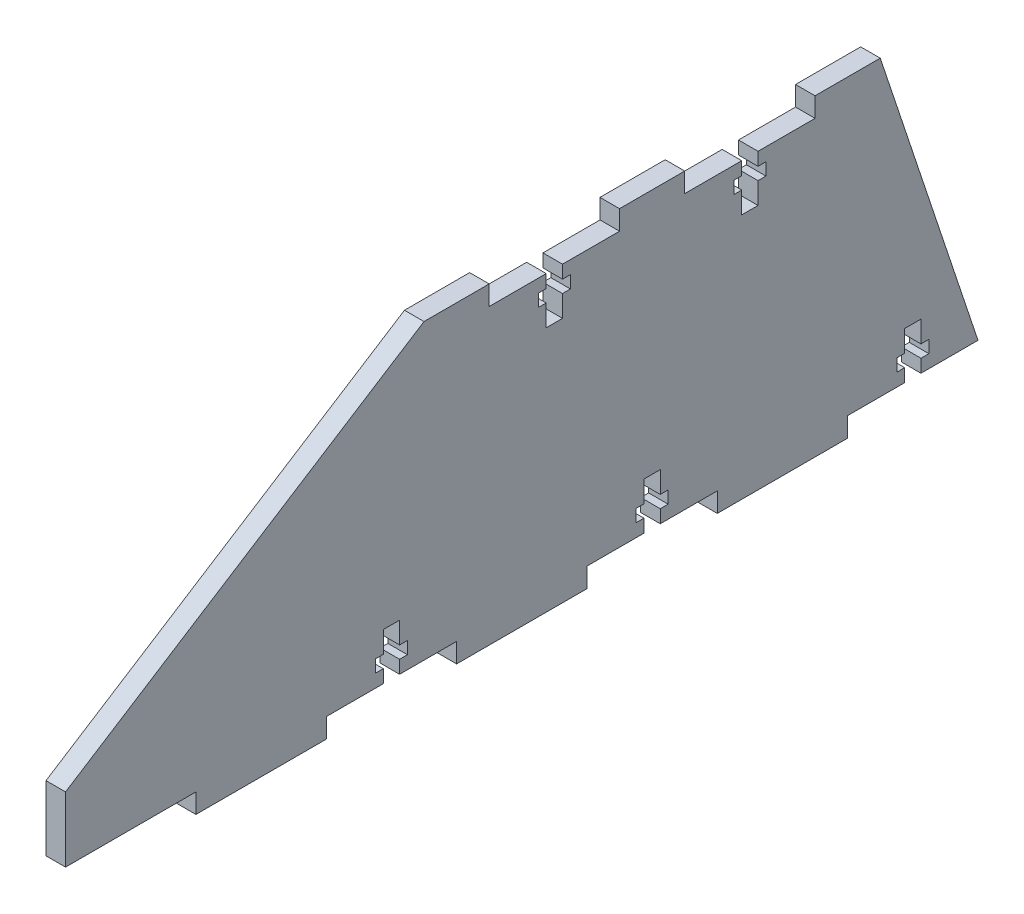
SolidWorks part; units mm, degrees
material "Acrylic (Medium-high impact)"
ref_plane "Front" through (0, 0, 0) normal (0, 0, 1) x (1, 0, 0)
ref_plane "Top" through (0, 0, 0) normal (0, 1, 0) x (1, 0, 0)
ref_plane "Right" through (0, 0, 0) normal (1, 0, 0) x (0, 0, -1)
sketch "Sketch1" plane through (0, 0, 0) normal (1, 0, 0) x (0, 0, -1)
  line L0 (-88.9, 3.81) -> (-63.5, 3.81)
  line L1 (-19.05, 60.96) -> (-6.35, 60.96)
  line L2 (-88.9, 16.51) -> (-88.9, 3.81)
  line L5 (-63.5, 3.81) -> (-63.5, 0)
  line L6 (-63.5, 0) -> (-38.1, 0)
  line L7 (-38.1, 0) -> (-38.1, 3.81)
  line L9 (-12.7, 3.81) -> (-12.7, 0)
  line L10 (-12.7, 0) -> (12.7, 0)
  line L11 (12.7, 0) -> (12.7, 3.81)
  line L13 (38.1, 3.81) -> (38.1, 0)
  line L14 (38.1, 0) -> (63.5, 0)
  line L15 (63.5, 0) -> (63.5, 3.81)
  line L16 (63.5, 3.81) -> (74.6125, 3.81)
  line L18 (-88.9, 16.51) -> (-19.05, 60.96)
  line L19 (69.85, 60.96) -> (88.9, 3.81)
  line L20 (114.3, 0) -> (114.3, 3.81) [skipped]
  line L21 (12.7, 3.81) -> (23.8125, 3.81)
  line L22 (88.9, 3.81) -> (88.9, 0) [skipped]
  line L23 (88.9, 0) -> (114.3, 0) [skipped]
  line L24 (74.6125, 3.81) -> (74.6125, 6.35)
  line L25 (74.6125, 6.35) -> (73.0758, 6.35)
  line L26 (73.0758, 6.35) -> (73.0758, 8.763)
  line L27 (73.0758, 8.763) -> (74.6125, 8.763)
  line L28 (74.6125, 8.763) -> (74.6125, 12.954)
  line L29 (74.6125, 12.954) -> (77.7875, 12.954)
  line L30 (77.7875, 12.954) -> (77.7875, 8.763)
  line L31 (77.7875, 8.763) -> (79.3242, 8.763)
  line L32 (79.3242, 8.763) -> (79.3242, 6.35)
  line L33 (79.3242, 6.35) -> (77.7875, 6.35)
  line L34 (77.7875, 6.35) -> (77.7875, 3.81)
  line L35 (77.7875, 3.81) -> (88.9, 3.81)
  line L36 (-38.1, 3.81) -> (-12.7, 3.81) [skipped]
  line L37 (12.7, 3.81) -> (38.1, 3.81) [skipped]
  line L38 (23.8125, 3.81) -> (23.8125, 6.35)
  line L39 (23.8125, 6.35) -> (22.2758, 6.35)
  line L40 (22.2758, 6.35) -> (22.2758, 8.763)
  line L41 (22.2758, 8.763) -> (23.8125, 8.763)
  line L42 (23.8125, 8.763) -> (23.8125, 12.954)
  line L43 (26.9875, 12.954) -> (26.9875, 8.763)
  line L44 (23.8125, 12.954) -> (26.9875, 12.954)
  line L45 (26.9875, 8.763) -> (28.5242, 8.763)
  line L46 (28.5242, 8.763) -> (28.5242, 6.35)
  line L47 (28.5242, 6.35) -> (26.9875, 6.35)
  line L48 (26.9875, 6.35) -> (26.9875, 3.81)
  line L50 (-38.1, 3.81) -> (-26.9875, 3.81)
  line L51 (-26.9875, 3.81) -> (-26.9875, 6.35)
  line L52 (-26.9875, 6.35) -> (-28.5242, 6.35)
  line L53 (-28.5242, 6.35) -> (-28.5242, 8.763)
  line L54 (-28.5242, 8.763) -> (-26.9875, 8.763)
  line L55 (-26.9875, 8.763) -> (-26.9875, 12.954)
  line L56 (-23.8125, 12.954) -> (-23.8125, 8.763)
  line L57 (-26.9875, 12.954) -> (-23.8125, 12.954)
  line L58 (-23.8125, 8.763) -> (-22.2758, 8.763)
  line L59 (-22.2758, 8.763) -> (-22.2758, 6.35)
  line L60 (-22.2758, 6.35) -> (-23.8125, 6.35)
  line L61 (-23.8125, 6.35) -> (-23.8125, 3.81)
  line L62 (-23.8125, 3.81) -> (-12.7, 3.81)
  line L63 (63.5, 3.81) -> (12.7, 3.81) construction
  line L64 (-23.8125, 3.81) -> (-12.7, 3.81) [skipped]
  line L65 (26.9875, 3.81) -> (38.1, 3.81)
  line L66 (26.9875, 3.81) -> (38.1, 3.81) [skipped]
  line L67 (-6.35, 60.96) -> (-6.35, 57.15)
  line L69 (19.05, 57.15) -> (19.05, 60.96)
  line L70 (31.75, 60.96) -> (31.75, 57.15)
  line L72 (57.15, 57.15) -> (57.15, 60.96)
  line L73 (19.05, 60.96) -> (31.75, 60.96)
  line L74 (57.15, 60.96) -> (69.85, 60.96)
  line L75 (-6.35, 57.15) -> (4.7625, 57.15)
  line L76 (4.7625, 57.15) -> (4.7625, 54.61)
  line L77 (4.7625, 54.61) -> (3.2258, 54.61)
  line L78 (3.2258, 54.61) -> (3.2258, 52.197)
  line L79 (3.2258, 52.197) -> (4.7625, 52.197)
  line L80 (4.7625, 52.197) -> (4.7625, 48.006)
  line L81 (4.7625, 48.006) -> (7.9375, 48.006)
  line L82 (7.9375, 48.006) -> (7.9375, 52.197)
  line L83 (7.9375, 52.197) -> (9.4742, 52.197)
  line L84 (9.4742, 52.197) -> (9.4742, 54.61)
  line L85 (9.4742, 54.61) -> (7.9375, 54.61)
  line L86 (7.9375, 54.61) -> (7.9375, 57.15)
  line L87 (7.9375, 57.15) -> (19.05, 57.15)
  line L88 (42.8625, 57.15) -> (42.8625, 54.61)
  line L89 (42.8625, 54.61) -> (41.3258, 54.61)
  line L90 (41.3258, 54.61) -> (41.3258, 52.197)
  line L91 (41.3258, 52.197) -> (42.8625, 52.197)
  line L92 (42.8625, 52.197) -> (42.8625, 48.006)
  line L93 (42.8625, 48.006) -> (46.0375, 48.006)
  line L94 (46.0375, 48.006) -> (46.0375, 52.197)
  line L95 (46.0375, 52.197) -> (47.5742, 52.197)
  line L96 (47.5742, 52.197) -> (47.5742, 54.61)
  line L97 (47.5742, 54.61) -> (46.0375, 54.61)
  line L98 (46.0375, 54.61) -> (46.0375, 57.15)
  line L99 (46.0375, 57.15) -> (57.15, 57.15)
  line L101 (4.7625, 57.15) -> (42.8625, 57.15) construction
  line L102 (31.75, 57.15) -> (42.8625, 57.15) [skipped]
  line L103 (31.75, 57.15) -> (42.8625, 57.15)
  point P0 (76.2, 12.954)
  point P92 (6.35, 48.006)
  dimension "D1" = 57.15
  dimension "D2" = 88.9
  dimension "D3" = 25.4
  dimension "D4" = 4
  dimension "D5" = 3.81
  dimension "D6" = 12.7
  dimension "D7" = 69.85
  dimension "D8" = 3.175
  dimension "D9" = 9.144
  dimension "D10" = 2.413
  dimension "D11" = 6.2484
  dimension "D12" = 2.54
  dimension "D13" = 177.8
  dimension "D14" = 12.7
  dimension "D16" = 50.8
  dimension "D17" = 3.81
  dimension "D18" = 25.4
  dimension "D19" = 12.7
  dimension "D20" = 2
  dimension "D21" = 38.1
  dimension "D22" = 9.144
  dimension "D15" = 3
extrude "Boss-Extrude1" add sketch "Sketch1" along normal blind 3.81 contours L9 L10 L11 L21 L38 L39 L40 L41 L42 L44 L43 L45 L46 L47 L48 L65 L13 L14 L15 L16 L24 L25 L26 L27 L28 L29 L30 L31 L32 L33 L34 L35 L19 L74 L72 L99 L98 L97 L96 L95 L94 L93 L92 L91 L90 L89 L88 L103 L70 L73 L69 L87 L86 L85 L84 L83 L82 L81 L80 L79 L78 L77 L76 L75 L67 L1 L18 L2 L0 L5 L6 L7 L50 L51 L52 L53 L54 L55 L57 L56 L58 L59 L60 L61 L62
